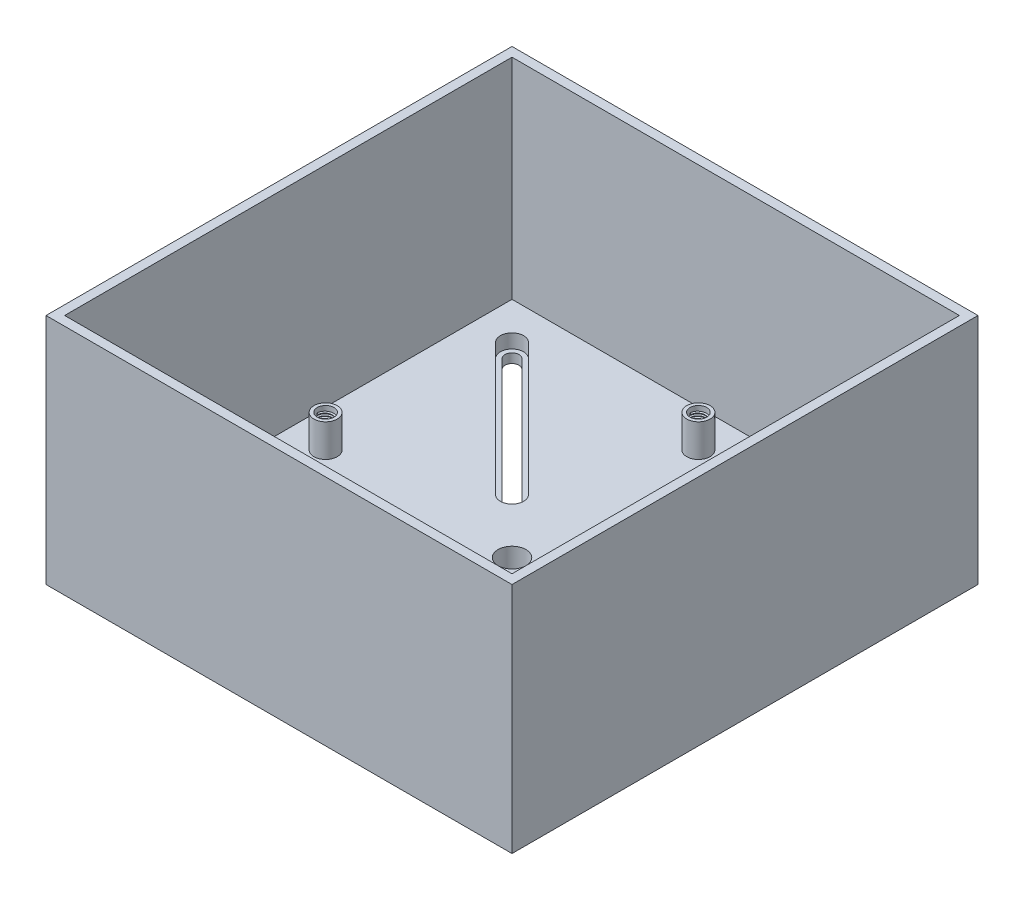
SolidWorks part; units mm, degrees
ref_plane "Ön Düzlem" through (0, 0, 0) normal (0, 0, 1) x (1, 0, 0)
ref_plane "Üst Düzlem" through (0, 0, 0) normal (0, 1, 0) x (1, 0, 0)
ref_plane "Sağ Düzlem" through (0, 0, 0) normal (1, 0, 0) x (0, 0, -1)
sketch "Çizim1" plane through (0, 0, 0) normal (0, 1, 0) x (1, 0, 0)
  line L0 (-40, 40) -> (-11.7157, 11.7157) construction
  line L1 (-50, 50) -> (50, 50)
  line L2 (-50, 50) -> (-50, -50)
  line L3 (-50, -50) -> (50, -50)
  line L4 (50, 50) -> (50, -50)
  line L5 (-50, 50) -> (50, -50) construction
  line L6 (-50, -50) -> (50, 50) construction
  line L9 (-38.2322, 41.7678) -> (-9.948, 13.4835)
  line L12 (-41.7678, 38.2322) -> (-13.4835, 9.948)
  line L13 (40, -40) -> (11.7157, -11.7157) construction
  line L14 (38.2322, -41.7678) -> (9.948, -13.4835)
  line L15 (41.7678, -38.2322) -> (13.4835, -9.948)
  line L16 (-38.9393, 41.0607) -> (-10.6551, 12.7764)
  line L17 (-41.0607, 38.9393) -> (-12.7764, 10.6551)
  line L18 (38.9393, -41.0607) -> (10.6551, -12.7764)
  line L19 (41.0607, -38.9393) -> (12.7764, -10.6551)
  line L21 (40, 35) -> (44.3301, 37.5)
  line L22 (44.3301, 37.5) -> (44.3301, 42.5)
  line L23 (44.3301, 42.5) -> (40, 45)
  line L24 (40, 45) -> (35.6699, 42.5)
  line L25 (35.6699, 42.5) -> (35.6699, 37.5)
  line L26 (35.6699, 37.5) -> (40, 35)
  circle A1 centre (40, 0) radius 2.5
  circle A2 centre (-40, 0) radius 2.5
  circle A3 centre (0, 40) radius 2.5
  circle A4 centre (0, -40) radius 2.5
  circle A6 centre (40, 40) radius 5
  arc A13 (-38.2322, 41.7678) -> (-41.7678, 38.2322) centre (-40, 40) ccw
  arc A14 (-13.4835, 9.948) -> (-9.948, 13.4835) centre (-11.7157, 11.7157) ccw
  arc A15 (38.2322, -41.7678) -> (41.7678, -38.2322) centre (40, -40) ccw
  arc A16 (13.4835, -9.948) -> (9.948, -13.4835) centre (11.7157, -11.7157) ccw
  arc A17 (-12.7764, 10.6551) -> (-10.6551, 12.7764) centre (-11.7157, 11.7157) ccw
  arc A18 (-38.9393, 41.0607) -> (-41.0607, 38.9393) centre (-40, 40) ccw
  arc A19 (12.7764, -10.6551) -> (10.6551, -12.7764) centre (11.7157, -11.7157) ccw
  arc A20 (38.9393, -41.0607) -> (41.0607, -38.9393) centre (40, -40) ccw
  circle A21 centre (40, 40) radius 5 construction
  circle A22 centre (40, 40) radius 3
  circle A23 centre (-40, -40) radius 3
  circle A25 centre (0, 0) radius 3
  circle A27 centre (-19.8475, -19.8475) radius 2.5
  point P0 (0, 0)
  point P21 (-25.8579, 25.8579)
  point P27 (25.8579, -25.8579)
  point P58 (-19.8475, -19.8475)
  dimension "D3" = 1
  dimension "D12" = 5
  dimension "D13" = 5
  dimension "D14" = 6
  dimension "D15" = 6
  dimension "D16" = 28.5
  dimension "D1" = 100
  dimension "D2" = 100
  dimension "D5" = 10
  dimension "D6" = 10
  dimension "D7" = 10
  dimension "D8" = 10
  dimension "D9" = 10
  dimension "D10" = 5
  dimension "D11" = 40
  dimension "D4" = 1
extrude "Ekstrüzyon-İnce4" add sketch "Çizim1" along normal blind 50 thin contours L3 L4 L1 L2 thin type one direction reverse wall 2
extrude "Yükseklik-Ekstrüzyon1" add sketch "Çizim1<3>" along normal blind 2 contours L4 L1 L2 L3 A25 A16 L15 A15 L14 A14 L12 A13 L9 A6 A4 A3 A2 A1 | A4 | A23 | A3 | A2 | A1 | L25 L26 L21 L22 L23 L24 A22 | L21 A6 | L22 A6 | L23 A6 | L24 A6 | L25 A6 | L26 A6 | L12 A14 L9 A13 A18 L16 A17 L17 | L15 A16 L14 A15 A20 L18 A19 L19 region at (0, 0, -48.5858) region at (-24.4229, 0, -27.2928) region at (24.4229, 0, 27.2928) region at (37.9011, 0, -36.3646) region at (37.7002, 0, -36.0166) region at (42.2998, 0, -36.0166) region at (44.5997, 0, -40) region at (35.4003, 0, -40) region at (42.2998, 0, -43.9834) region at (37.7002, 0, -43.9834) region at (40, 0, 0) region at (-40, 0, 0) region at (0, 0, -40) region at (0, 0, 40)
sketch "Çizim1<3>" plane through (0, 0, 0) normal (0, 1, 0) x (1, 0, 0) same geometry as "Çizim1"
extrude "Yükseklik-Ekstrüzyon2" add sketch "Çizim1<4>" along normal blind 12 contours A2 | A3 | A1 | A4 region at (40, 0, 0) region at (-40, 0, 0) region at (0, 0, -40) region at (0, 0, 40)
sketch "Çizim1<4>" plane through (0, 0, 0) normal (0, 1, 0) x (1, 0, 0) same geometry as "Çizim1"
extrude "Yükseklik-Ekstrüzyon3" add sketch "Çizim1<5>" along normal blind 5 contours L4 L1 L2 L3 A25 A16 L15 A15 L14 A14 L12 A13 L9 A6 A4 A3 A2 A1 | A23 | L21 A6 | L22 A6 | L26 A6 | L25 A6 | L24 A6 | L23 A6 region at (0, 0, -48.5858) region at (37.7002, 0, -36.0166) region at (42.2998, 0, -36.0166) region at (44.5997, 0, -40) region at (35.4003, 0, -40) region at (42.2998, 0, -43.9834) region at (37.7002, 0, -43.9834)
sketch "Çizim1<5>" plane through (0, 0, 0) normal (0, 1, 0) x (1, 0, 0) same geometry as "Çizim1"
sketch "Çizim2" plane through (0, 5, 0) normal (0, 1, 0) x (1, 0, 0)
  circle A2 centre (-40, -40) radius 2.5
  circle A3 centre (-40, -40) radius 2.5
  circle A4 centre (-40, -40) radius 3 construction
  circle A5 centre (-40, -40) radius 3
  dimension "D1" = 0.5
extrude "Yükseklik-Ekstrüzyon4" add sketch "Çizim2" against normal blind 2
sketch "Çizim3" plane through (0, 12, 0) normal (0, 1, 0) x (1, 0, 0)
  circle A2 centre (40, 0) radius 1.8
  circle A3 centre (40, 0) radius 1.8
  dimension "D1" = 0.7
extrude "Kes-Ekstrüzyon1" cut sketch "Çizim3" against normal blind 8
sketch "Çizim7" plane through (0, 12, 0) normal (0, 1, 0) x (1, 0, 0)
  circle A2 centre (0, -40) radius 1.8
  circle A3 centre (0, -40) radius 1.8
  dimension "D1" = 0.7
extrude "Kes-Ekstrüzyon3" cut sketch "Çizim7" against normal blind 8
sketch "Çizim8" plane through (0, 12, 0) normal (0, 1, 0) x (1, 0, 0)
  circle A2 centre (-40, 0) radius 1.8
  circle A3 centre (-40, 0) radius 1.8
  dimension "D1" = 0.7
extrude "Kes-Ekstrüzyon4" cut sketch "Çizim8" against normal blind 8
sketch "Çizim9" plane through (0, 12, 0) normal (0, 1, 0) x (1, 0, 0)
  circle A2 centre (0, 40) radius 1.8
  circle A3 centre (0, 40) radius 1.8
  dimension "D1" = 0.7
extrude "Kes-Ekstrüzyon5" cut sketch "Çizim9" against normal blind 8
thread "Diş1" pitch 0.5 method extrude profile "Diş Profili3" start angle 0, offset 1, length 7, pitch 0.5, diameter 3.6
ref_plane "Düzlem3" through (-1.8, 11, -40) normal (0, 0, 1) x (-1, 0, 0)
sketch "Diş Profili3" plane through (-1.8, 11, -40) normal (0, 0, 1) x (-1, 0, 0)
  line L0 (0, 0) -> (0, 0.5) construction
  line L11 (0, 0) -> (0, 0.4375)
  line L12 (0, 0.4375) -> (-0.2706, 0.2812)
  line L13 (-0.2706, 0.2812) -> (-0.2706, 0.1562)
  line L15 (-0.2706, 0.1562) -> (0, 0)
  line L17 (-0.2706, 0.2187) -> (0, 0.2187) construction
  point P2 (0, 0)
  dimension "Pitch" = 0.5
  dimension "Profile_Angle" = 60
  dimension "Profile_Land" = 0.125
  dimension "Profile_Height" = 0.2706
thread "Diş2" pitch 0.5 method extrude profile "Diş Profili4" start angle 0, offset 1, length 7, pitch 0.5, diameter 3.6
ref_plane "Düzlem4" through (-41.8, 11, 0) normal (0, 0, 1) x (-1, 0, 0)
sketch "Diş Profili4" plane through (-41.8, 11, 0) normal (0, 0, 1) x (-1, 0, 0)
  line L0 (0, 0) -> (0, 0.5) construction
  line L11 (0, 0) -> (0, 0.4375)
  line L12 (0, 0.4375) -> (-0.2706, 0.2812)
  line L13 (-0.2706, 0.2812) -> (-0.2706, 0.1562)
  line L15 (-0.2706, 0.1562) -> (0, 0)
  line L17 (-0.2706, 0.2187) -> (0, 0.2187) construction
  point P2 (0, 0)
  dimension "Pitch" = 0.5
  dimension "Profile_Angle" = 60
  dimension "Profile_Land" = 0.125
  dimension "Profile_Height" = 0.2706
thread "Diş3" pitch 0.5 method extrude profile "Diş Profili5" start angle 0, offset 1, length 7, pitch 0.5, diameter 3.6
ref_plane "Düzlem5" through (-1.8, 11, 40) normal (0, 0, 1) x (-1, 0, 0)
sketch "Diş Profili5" plane through (-1.8, 11, 40) normal (0, 0, 1) x (-1, 0, 0)
  line L0 (0, 0) -> (0, 0.5) construction
  line L11 (0, 0) -> (0, 0.4375)
  line L12 (0, 0.4375) -> (-0.2706, 0.2812)
  line L13 (-0.2706, 0.2812) -> (-0.2706, 0.1562)
  line L15 (-0.2706, 0.1562) -> (0, 0)
  line L17 (-0.2706, 0.2187) -> (0, 0.2187) construction
  point P2 (0, 0)
  dimension "Pitch" = 0.5
  dimension "Profile_Angle" = 60
  dimension "Profile_Land" = 0.125
  dimension "Profile_Height" = 0.2706
thread "Diş4" pitch 0.5 method extrude profile "Diş Profili6" start angle 0, offset 1, length 7, pitch 0.5, diameter 3.6
ref_plane "Düzlem6" through (38.2, 11, 0) normal (0, 0, 1) x (-1, 0, 0)
sketch "Diş Profili6" plane through (38.2, 11, 0) normal (0, 0, 1) x (-1, 0, 0)
  line L0 (0, 0) -> (0, 0.5) construction
  line L11 (0, 0) -> (0, 0.4375)
  line L12 (0, 0.4375) -> (-0.2706, 0.2812)
  line L13 (-0.2706, 0.2812) -> (-0.2706, 0.1562)
  line L15 (-0.2706, 0.1562) -> (0, 0)
  line L17 (-0.2706, 0.2187) -> (0, 0.2187) construction
  point P2 (0, 0)
  dimension "Pitch" = 0.5
  dimension "Profile_Angle" = 60
  dimension "Profile_Land" = 0.125
  dimension "Profile_Height" = 0.2706
sketch "Çizim27" plane through (0, 5, 0) normal (0, 1, 0) x (1, 0, 0)
  circle A0 centre (-19.8475, -19.8475) radius 2.5 construction
  circle A1 centre (-19.8475, -19.8475) radius 2.5
extrude "Yükseklik-Ekstrüzyon5" add sketch "Çizim27" against normal through all and the other way blind 5 contours A1
